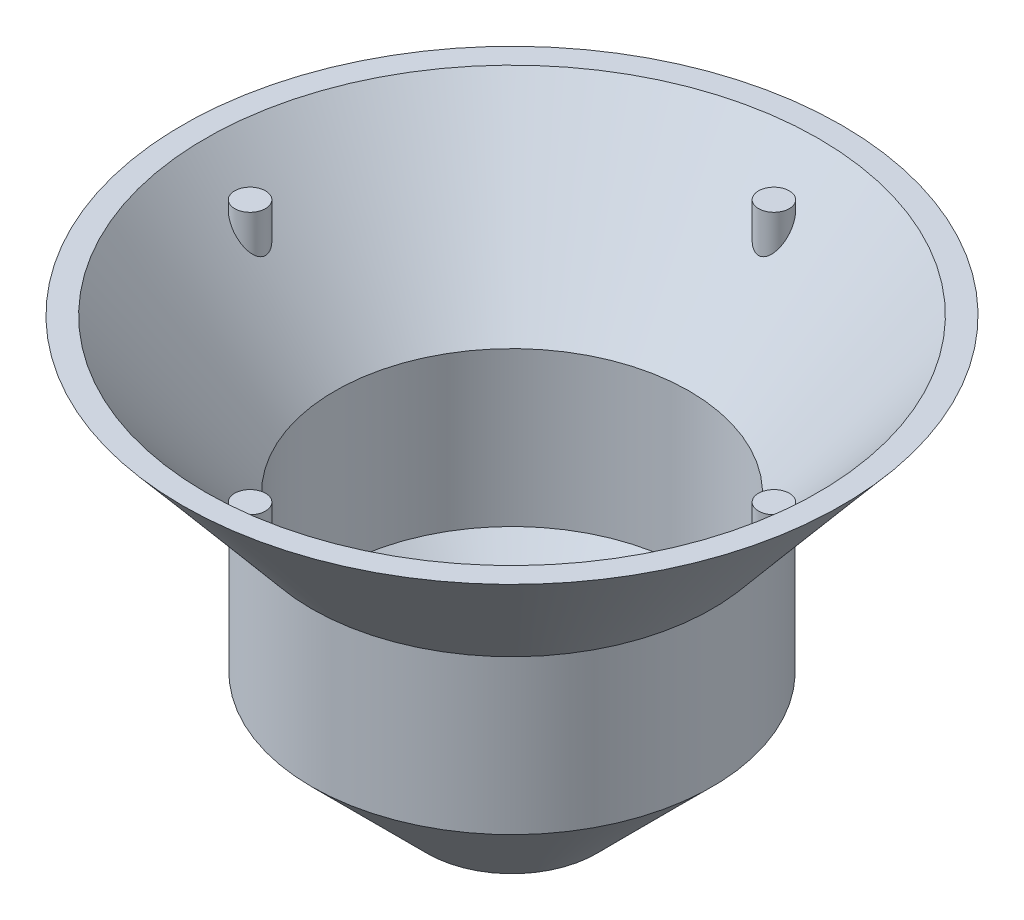
SolidWorks part; units mm, degrees
ref_plane "Front Plane" through (0, 0, 0) normal (0, 0, 1) x (1, 0, 0)
ref_plane "Top Plane" through (0, 0, 0) normal (0, 1, 0) x (1, 0, 0)
ref_plane "Right Plane" through (0, 0, 0) normal (1, 0, 0) x (0, 0, -1)
sketch "Sketch1" plane through (0, 0, 0) normal (0, 1, 0) x (1, 0, 0)
  circle A0 centre (0, 0) radius 13
  circle A1 centre (0, 0) radius 11.5
  dimension "D1" = 26
  dimension "D2" = 1.5
extrude "Boss-Extrude1" add sketch "Sketch1" along normal blind 10
ref_axis "Axis1" through (0, 18.9308, 0) along (0, -1, 0)
sketch "Sketch4" plane through (0, 0, 0) normal (0, 0, 1) x (1, 0, 0)
  line L0 (-13, 10) -> (-21.391, 20)
  line L1 (-21.391, 20) -> (-19.891, 20)
  line L2 (-19.891, 20) -> (-11.5, 10)
  line L3 (13, 10) -> (-13, 10) construction
  line L4 (-11.5, 10) -> (-13, 10)
  line L5 (11.5, 10) -> (-11.5, 10) construction
  dimension "D1" = 1.5
  dimension "D2" = 130
  dimension "D3" = 10
revolve "Revolve1" add sketch "Sketch4" angle 360 about axis through (0, 18.9308, 0) along (0, -1, 0)
sketch "Sketch5" plane through (0, 20, 0) normal (0, 1, 0) x (1, 0, 0)
  line L0 (0, 18) -> (0, -18) construction
  line L1 (-18, 0) -> (18, 0) construction
  circle A0 centre (0, 0) radius 18 construction
  circle A1 centre (-17, 0) radius 1
  dimension "D1" = 36
  dimension "D2" = 1
extrude "Boss-Extrude2" add sketch "Sketch5" along normal up to surface (1.4103 mm away) from offset 2 offset against normal yes
pattern_circular "CirPattern1" count 4 over 360 about axis through (0, 0, 0) along (0, 1, 0) of "Boss-Extrude2"
sketch "Sketch6" plane through (0, 0, 0) normal (0, 0, 1) x (1, 0, 0)
  line L0 (-13, 0) -> (-5.5, -7.5)
  line L1 (-5.5, -7.5) -> (-4, -7.5)
  line L2 (-4, -7.5) -> (-11.5, 0)
  line L3 (-13, 0) -> (13, 0) construction
  line L4 (-11.5, 0) -> (-13, 0)
  line L5 (13, 0) -> (-13, 0) construction
  dimension "D1" = 1.5
  dimension "D2" = 45
  dimension "D3" = 7.5
revolve "Revolve2" add sketch "Sketch6" angle 360 about axis through (0, 18.9308, 0) along (0, -1, 0)
